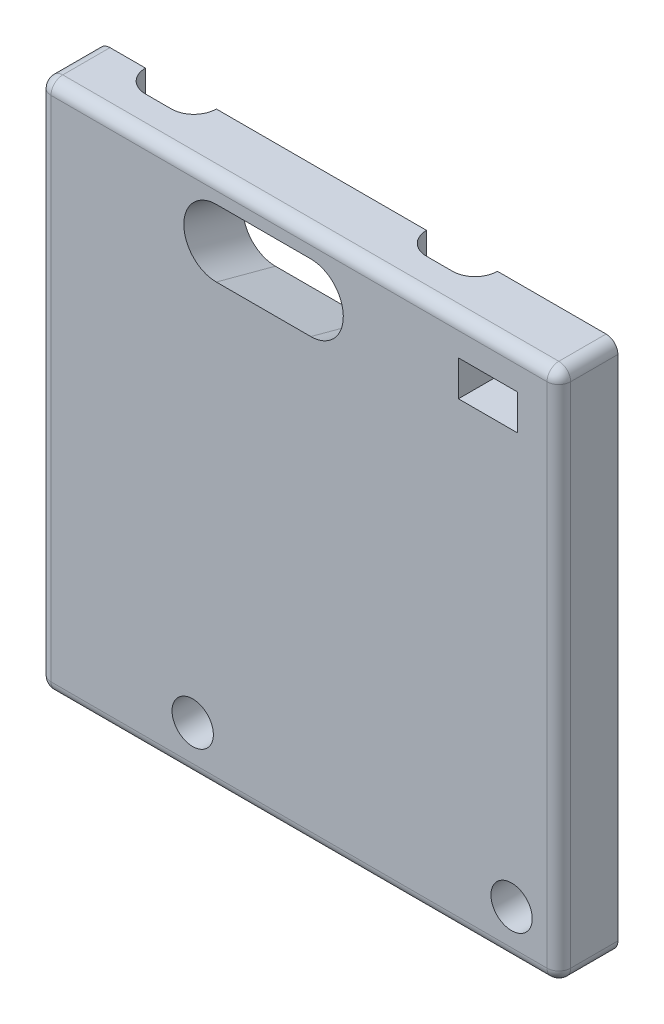
SolidWorks part; units mm, degrees
ref_plane "Front Plane" through (0, 0, 0) normal (0, 0, 1) x (1, 0, 0)
ref_plane "Top Plane" through (0, 0, 0) normal (0, 1, 0) x (1, 0, 0)
ref_plane "Right Plane" through (0, 0, 0) normal (1, 0, 0) x (0, 0, -1)
sketch "Sketch1" plane through (0, 0, 0) normal (0, 0, 1) x (1, 0, 0)
  line L1 (-22, 22.5) -> (22, 22.5)
  line L2 (-22, 22.5) -> (-22, -22.5)
  line L3 (-22, -22.5) -> (22, -22.5)
  line L4 (22, 22.5) -> (22, -22.5)
  line L5 (-22, 22.5) -> (22, -22.5) construction
  line L6 (-22, -22.5) -> (22, 22.5) construction
  point P0 (0, 0)
  dimension "D1" = 44
  dimension "D2" = 45
extrude "Base" add sketch "Sketch1" along normal blind 5
sketch "Sketch2" plane through (0, 22.5, 0) normal (0, 1, 0) x (1, 0, 0)
  line L0 (22, 0) -> (-22, 0) construction
  line L1 (-18, 0) -> (-12, 0)
  line L2 (0, 0) -> (0, -5) construction
  line L3 (22, -5) -> (-22, -5) construction
  line L5 (-16.1, -1.9) -> (-13.9, -1.9)
  line L6 (-18, 0) -> (-18, -5) construction
  line L7 (-3.1, 0) -> (-3.1, -5) construction
  line L8 (9.9, -1.9) -> (7.7, -1.9)
  line L9 (11.8, 0) -> (5.8, 0)
  arc A2 (-16.1, -1.9) -> (-18, 0) centre (-16.1, 0) cw
  arc A3 (-12, 0) -> (-13.9, -1.9) centre (-13.9, 0) cw
  arc A4 (9.9, -1.9) -> (11.8, 0) centre (9.9, 0) ccw
  arc A5 (5.8, 0) -> (7.7, -1.9) centre (7.7, 0) ccw
  point P0 (-15, 0)
  point P15 (-15, -1.9)
  dimension "D1" = 15
  dimension "D2" = 6
  dimension "D3" = 1.9
  dimension "D4" = 11.9
extrude "Wire Grooves" cut sketch "Sketch2" against normal through all
sketch "Sketch4" plane through (0, 0, 0) normal (0, 0, -1) x (-1, 0, 0)
  line L0 (0, 22.5) -> (0, -22.5) construction
  line L3 (-22, 16.5291) -> (22, 16.5291) construction
  line L4 (-22, -22.5) -> (-22, 22.5) construction
  line L5 (22, 22.5) -> (22, -22.5) construction
  line L6 (-22, 22.5) -> (-11.8, 22.5) construction
  line L7 (12, -22.5) -> (-5.8, -22.5) construction
  dimension "D1" = 5.9709
ref_plane "Screw Insertion Hole Reference" through (0, 1.1072, 4.1323) normal (0, -0.2588, -0.9659) x (-1, 0, 0)
sketch "Sketch3" plane through (0, 0.5961, 4.2692) normal (0, -0.2588, -0.9659) x (-1, 0, 0)
  line L0 (0, 0.5291) -> (0, 22.2625) construction
  line L1 (-1, 16.2925) -> (7, 16.2925) construction
  line L2 (-22, 22.2625) -> (-11.8, 22.2625) construction
  line L3 (-1, 19.0425) -> (7, 19.0425)
  line L4 (-1, 13.5425) -> (7, 13.5425)
  line L5 (-5.8, 22.2625) -> (12, 22.2625) construction
  arc A1 (-1, 19.0425) -> (-1, 13.5425) centre (-1, 16.2925) ccw
  arc A2 (7, 13.5425) -> (7, 19.0425) centre (7, 16.2925) ccw
  point P5 (3, 16.2925)
  dimension "D1" = 5.97
  dimension "D2" = 2.75
  dimension "D3" = 8
  dimension "D4" = 3
extrude "Screw Insertion Hole" cut sketch "Sketch3" against normal through all both and the other way through all
sketch "Sketch5" plane through (0, 0, 0) normal (0, 0, -1) x (-1, 0, 0)
  line L1 (-22, 22.5) -> (-11.8, 22.5) construction
  line L3 (0, 22.5) -> (0, -22.5) construction
  line L7 (-18.5, 19.5) -> (-13.5, 19.5)
  line L8 (-18.5, 19.5) -> (-18.5, 16.5)
  line L9 (-18.5, 16.5) -> (-13.5, 16.5)
  line L10 (-13.5, 19.5) -> (-13.5, 16.5)
  line L11 (-18.5, 19.5) -> (-13.5, 16.5) construction
  line L12 (-18.5, 16.5) -> (-13.5, 19.5) construction
  line L16 (-22, 22.5) -> (-11.8, 22.5) construction
  line L20 (12, -22.5) -> (-5.8, -22.5) construction
  line L21 (-4, 22.5) -> (-4, -22.5) construction
  line L22 (-5.8, 22.5) -> (12, 22.5) construction
  line L23 (12, -22.5) -> (-5.8, -22.5) construction
  point P12 (-16, 18)
  dimension "D1" = 5
  dimension "D2" = 3
  dimension "D3" = 3
  dimension "D4" = 16
  dimension "D5" = 4
extrude "Zip Tie Slots" cut sketch "Sketch5" against normal through all
sketch "Sketch6" plane through (0, 0, 0) normal (0, 0, -1) x (-1, 0, 0)
  line L1 (-22, -22.5) -> (-22, 22.5) construction
  line L2 (12, -22.5) -> (-5.8, -22.5) construction
  line L4 (-4.5, 22.5) -> (-4.5, -22.5) construction
  line L6 (-22, 22.5) -> (-11.8, 22.5) construction
  circle A0 centre (-18, -18.5) radius 1.75
  circle A2 centre (9, -18.5) radius 1.75
  dimension "D1" = 3.5
  dimension "D2" = 4
  dimension "D3" = 4
  dimension "D4" = 4.5
extrude "Mount Clamping Holes" cut sketch "Sketch6" against normal through all
fillet "Edge Fillets" radius 1 8 edges at (-22, 0, 5) (22, 0, 5) (0, -22.5, 5) (0, 22.5, 5) (22, 22.5, 2.5) (22, -22.5, 2.5) (-22, -22.5, 2.5) (-22, 22.5, 2.5)
